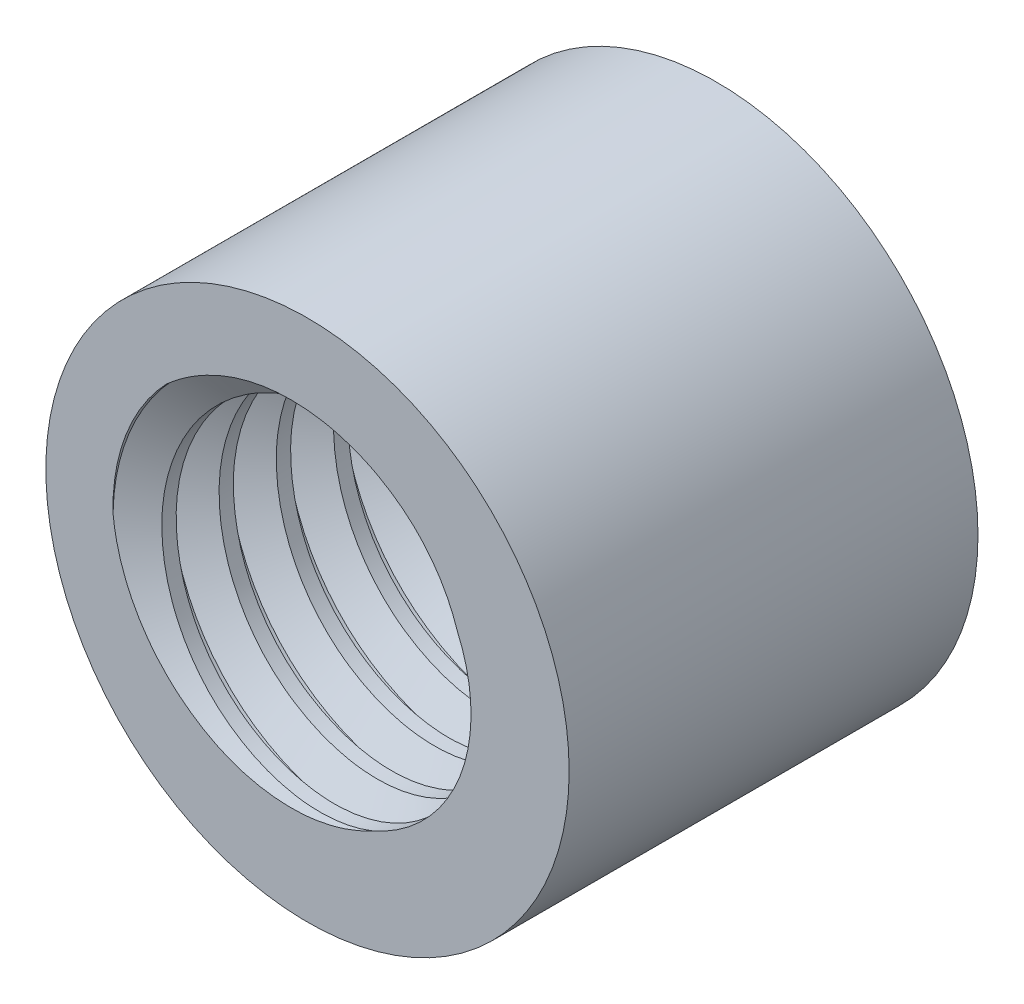
SolidWorks part; units mm, degrees
material "Brass"
ref_plane "Front Plane" through (0, 0, 0) normal (0, 0, 1) x (1, 0, 0)
ref_plane "Top Plane" through (0, 0, 0) normal (0, 1, 0) x (1, 0, 0)
ref_plane "Right Plane" through (0, 0, 0) normal (1, 0, 0) x (0, 0, -1)
sketch "Sketch1" plane through (0, 0, 0) normal (0, 0, 1) x (1, 0, 0)
  circle A0 centre (0, 0) radius 2
  circle A1 centre (0, 0) radius 3.2
  dimension "D1" = 4
  dimension "D2" = 6.4
extrude "Boss-Extrude1" add sketch "Sketch1" along normal blind 5
thread "Thread1" pitch 0.7 method cut profile "Thread Profile1" start angle 2, offset 1, length 10, pitch 0.7, diameter 4
ref_plane "Plane1" through (-1.9988, 0.0698, 6) normal (-0.0349, -0.9994, 0) x (-0.9994, 0.0349, 0)
sketch "Thread Profile1" plane through (-1.9988, 0.0698, 6) normal (-0.0349, -0.9994, 0) x (-0.9994, 0.0349, 0)
  line L0 (0, 0) -> (0, 0.7) construction
  line L1 (0, 0) -> (0.3789, 0.2187)
  line L2 (0.3789, 0.2187) -> (0.3789, 0.3062)
  line L3 (0.3789, 0.3062) -> (0, 0.525)
  line L4 (0.3789, 0.2625) -> (0, 0.2625) construction
  line L11 (0, 0) -> (0, 0.525)
  point P2 (0, 0)
  dimension "Pitch" = 0.7
  dimension "Profile_Angle" = 60
  dimension "Profile_Land" = 0.0875
  dimension "Profile_Height" = 0.3789
sketch "Sketch2" plane through (0, 0, 5) normal (0, 0, 1) x (1, 0, 0)
  circle A0 centre (0, 0) radius 3.2 construction
  arc A1 (-0.3182, 3.1841) -> (0.8405, 3.0877) centre (0.3744, 4.4959) ccw
  arc A2 (1.198, 2.9673) -> (2.1791, 2.3434) centre (2.4208, 3.8069) ccw
  arc A3 (2.4397, 2.0707) -> (3.0185, 1.0623) centre (3.9127, 2.2459) ccw
  arc A4 (3.1226, 0.6997) -> (3.1664, -0.4622) centre (4.5082, 0.1703) ccw
  arc A5 (3.0901, -0.8316) -> (2.589, -1.8808) centre (4.071, -1.9443) ccw
  arc A6 (2.3497, -2.1723) -> (1.4184, -2.8685) centre (2.7011, -3.6135) ccw
  arc A7 (1.071, -3.0155) -> (-0.0771, -3.1991) centre (0.7124, -4.4548) ccw
  arc A8 (-0.453, -3.1678) -> (-1.555, -2.7968) centre (-1.4394, -4.2756) ccw
  arc A9 (-1.8733, -2.5944) -> (-2.6766, -1.7538) centre (-3.2615, -3.117) ccw
  arc A10 (-2.8644, -1.4267) -> (-3.185, -0.309) centre (-4.3365, -1.2442) ccw
  arc A11 (-3.1993, 0.0679) -> (-2.9638, 1.2065) centre (-4.418, 0.9136) ccw
  arc A12 (-2.8013, 1.5469) -> (-2.0636, 2.4457) centre (-3.4874, 2.862) ccw
  arc A13 (-1.7615, 2.6715) -> (-0.6907, 3.1246) centre (-1.7579, 4.1549) ccw
  circle A14 centre (0, 0) radius 5.1115
  point P40 (0, 0)
  circle M14 centre (0, 0) radius 3.2
  dimension "D1" = 13
extrude "Cut-Extrude1" [suppressed] cut sketch "Sketch2" against normal through all contours A1 M14 | A13 M14 | A12 M14 | A11 M14 | A10 M14 | A9 M14 | A8 M14 | A7 M14 | A6 M14 | A5 M14 | A4 M14 | A3 M14 | A2 M14
